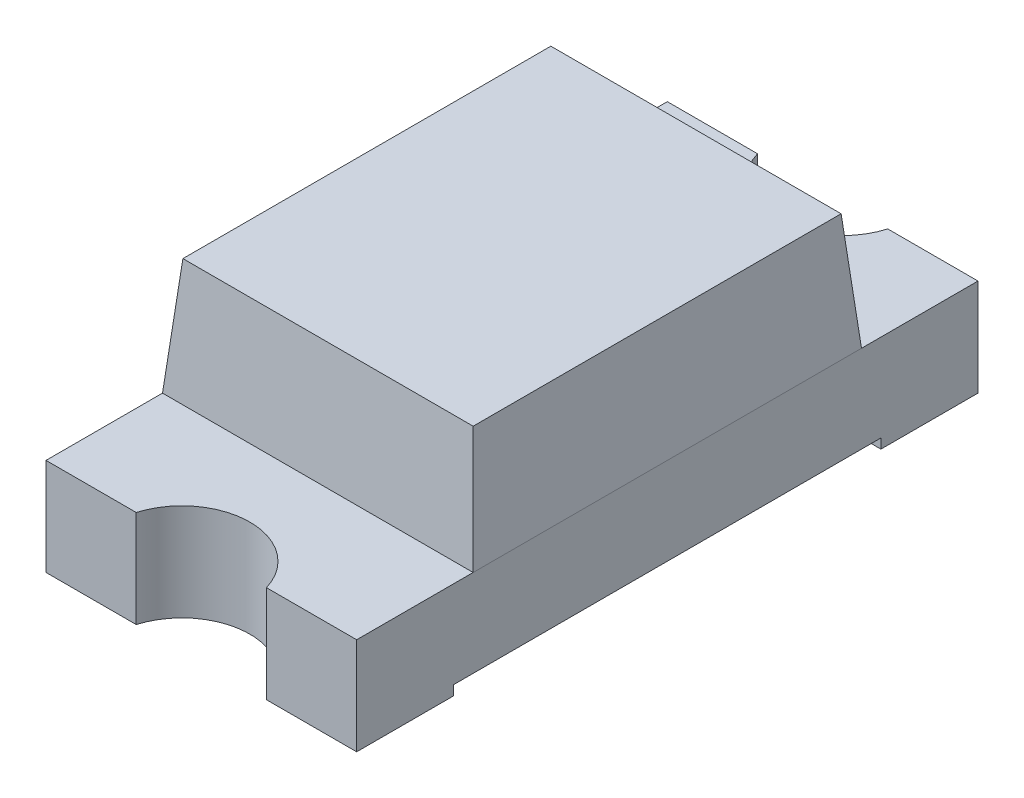
SolidWorks part; units mm, degrees
ref_plane "Front Plane" through (0, 0, 0) normal (0, 0, 1) x (1, 0, 0)
ref_plane "Top Plane" through (0, 0, 0) normal (0, 1, 0) x (1, 0, 0)
ref_plane "Right Plane" through (0, 0, 0) normal (1, 0, 0) x (0, 0, -1)
sketch "Sketch1" plane through (0, 0, 0) normal (1, 0, 0) x (0, 0, -1)
  line L0 (1.1, 0) -> (1.6, 0)
  line L1 (-1.6, 0.5) -> (1.6, 0.5)
  line L2 (-1.6, 0.5) -> (-1.6, 0)
  line L3 (-1.6, 0) -> (-1.1, 0)
  line L4 (1.6, 0.5) -> (1.6, 0)
  line L5 (-1.1, 0.05) -> (1.1, 0.05)
  line L6 (-1.1, 0.05) -> (-1.1, 0)
  line L8 (1.1, 0.05) -> (1.1, 0)
  dimension "D1" = 3.2
  dimension "D2" = 0.5
  dimension "D3" = 0.05
  dimension "D4" = 2.2
  dimension "D5" = 1.1
extrude "Extrude1" add sketch "Sketch1" along normal blind 0.8 and the other way blind 0.8
sketch "Sketch2" plane through (0, 0, 0) normal (0, 1, 0) x (1, 0, 0)
  circle A0 centre (0, 1.7) radius 0.35
  circle A1 centre (0, -1.7) radius 0.35
extrude "Cut-Extrude1" cut sketch "Sketch2" along normal through all
sketch "Sketch3" plane through (0, 0.5, 0) normal (0, 1, 0) x (-1, 0, 0)
  line L1 (0.4574, -1) -> (0.2774, -1)
  line L2 (0.4574, -1) -> (0.4574, -0.4507)
  line L3 (0.225, -0.225) -> (-0.225, -0.225)
  line L4 (0.2774, -1) -> (0.2774, -0.6307)
  line L5 (0.4574, -0.4507) -> (-0.2764, -0.4507)
  line L7 (0.2774, -0.6307) -> (-0.2764, -0.6307)
  line L8 (-0.2764, -0.4507) -> (-0.2764, -0.6307)
  line L9 (0.225, -0.225) -> (0.225, 0.4637)
  line L10 (0.075, 0.225) -> (-0.225, 0.225)
  line L11 (-0.225, -0.225) -> (-0.225, 0.225)
  line L13 (0.225, 0.4637) -> (0.225, 0.7354)
  line L15 (0.075, 0.225) -> (0.075, 0.525)
  line L16 (0.075, 0.525) -> (-0.2794, 0.525)
  line L17 (0.225, 0.7354) -> (0.225, 0.675)
  line L18 (0.225, 0.675) -> (-0.3274, 0.675)
  line L20 (-0.2794, 0.525) -> (-0.4774, 0.525)
  line L21 (-0.3274, 0.675) -> (-0.3274, 1)
  line L22 (-0.3274, 1) -> (-0.4774, 1)
  line L23 (-0.4774, 0.525) -> (-0.4774, 1)
  dimension "D1" = 0.45
  dimension "D2" = 0.45
  dimension "D3" = 0.225
  dimension "D4" = 0.225
  dimension "D5" = 0.15
  dimension "D6" = 0.15
  dimension "D7" = 0.15
  dimension "D8" = 0.3
  dimension "D9" = 1
  dimension "D10" = 1
  dimension "D11" = 0.18
  dimension "D12" = 0.18
extrude "Cut-Extrude2" cut sketch "Sketch3" against normal blind 0.005 contours L23 L20 L16 L15 L10 L11 L3 L9 L13 L18 L21 L22 | L5 L8 L7 L4 L1 L2 region at (-0.3674, 0.5, -0.9908) region at (0, 0.5, -0.2109)
sketch "Sketch4" plane through (0, 0.495, 0) normal (0, 1, 0) x (-1, 0, 0)
  line L1 (0.195, -0.195) -> (-0.195, -0.195)
  line L2 (0.195, -0.195) -> (0.195, 0.195)
  line L3 (0.195, 0.195) -> (-0.195, 0.195)
  line L4 (-0.195, -0.195) -> (-0.195, 0.195)
  dimension "D1" = 0.39
  dimension "D2" = 0.39
  dimension "D3" = 0.195
  dimension "D4" = 0.195
extrude "Extrude2" add sketch "Sketch4" along normal blind 0.25
sketch "Sketch5" plane through (0, 0.5, 0) normal (0, 1, 0) x (-1, 0, 0)
  line L0 (0.8, -1.6) -> (0.8, 1.6) construction
  line L1 (0.8, -1) -> (-0.8, -1)
  line L2 (0.8, -1) -> (0.8, 1)
  line L3 (0.8, 1) -> (-0.8, 1)
  line L4 (-0.8, -1) -> (-0.8, 1)
  line L5 (-0.8, -1.6) -> (-0.8, 1.6) construction
  dimension "D1" = 2
extrude "Extrude3" add sketch "Sketch5" along normal blind 0.6 draft 5 separate body
sketch "Component_Outline" plane through (0, 0, 0) normal (0, 1, 0) x (1, 0, 0)
  line L0 (0.3354, 1.6) -> (0.8, 1.6)
  line L1 (-0.8, -1.6) -> (-0.3354, -1.6)
  line L2 (-0.8, -1.6) -> (-0.8, 1.6)
  line L3 (-0.8, 1.6) -> (-0.3354, 1.6)
  line L4 (0.8, -1.6) -> (0.8, 1.6)
  line L5 (0.3354, -1.6) -> (0.8, -1.6)
  arc A0 (-0.3354, 1.6) -> (0.3354, 1.6) centre (0, 1.7) ccw
  arc A1 (-0.3354, 1.6) -> (0.3354, 1.6) centre (0, 1.7) ccw construction
  arc A2 (-0.3354, -1.6) -> (0.3354, -1.6) centre (0, -1.7) cw
  arc A3 (0.3354, -1.6) -> (-0.3354, -1.6) centre (0, -1.7) ccw construction
